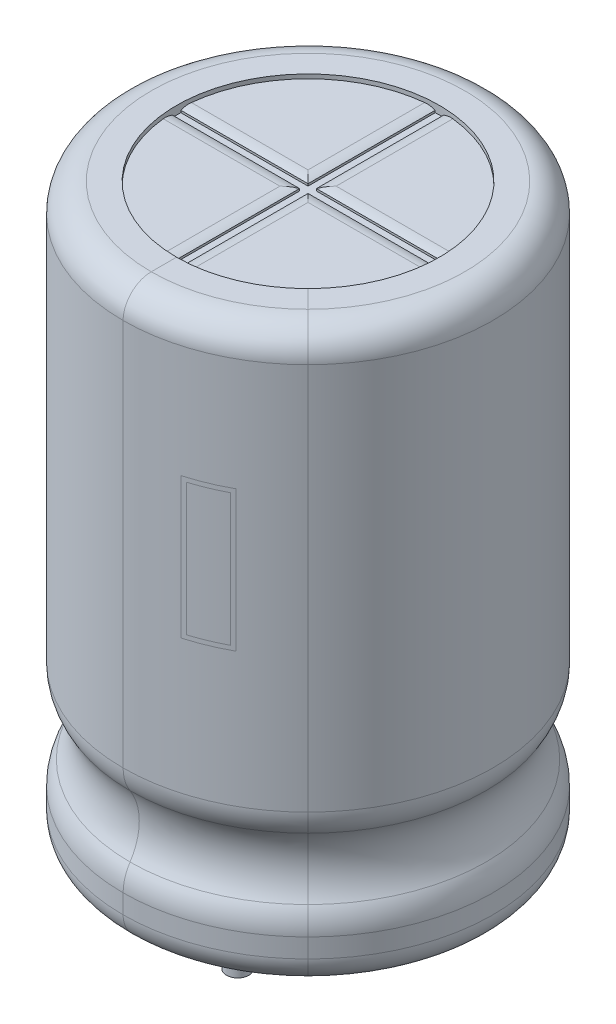
SolidWorks part; units mm, degrees
ref_plane "Front" through (0, 0, 0) normal (0, 0, 1) x (1, 0, 0)
ref_plane "Top" through (0, 0, 0) normal (0, 1, 0) x (1, 0, 0)
ref_plane "Right" through (0, 0, 0) normal (1, 0, 0) x (0, 0, -1)
sketch "Sketch1" plane through (0, 0, 0) normal (1, 0, 0) x (0, 0, -1)
  line L0 (0, 33.3732) -> (0, 0) construction
  line L1 (0, 0) -> (30.9962, 0) construction
  line L2 (0, 20) -> (4.675, 20)
  line L3 (4.675, 19) -> (4.675, 20.15)
  line L4 (5.575, 20.15) -> (4.675, 20.15)
  line L5 (6.575, 19.15) -> (6.575, 5.3721)
  line L6 (6.575, 1.5279) -> (6.575, 0.85)
  line L7 (5.425, -0.15) -> (5.575, -0.15)
  line L8 (5.425, 0) -> (5.425, -0.15)
  line L9 (5.425, 0) -> (0, 0)
  line L10 (0, 0) -> (0, 20)
  line L11 (0, 10) -> (2.9717, 10) construction
  line L12 (6, 3.45) -> (6, 1.4188) construction
  line L13 (0, 19) -> (4.675, 19)
  arc A0 (5.575, 20.15) -> (6.575, 19.15) centre (5.575, 19.15) cw
  arc A1 (6.575, 5.3721) -> (6.3286, 4.5483) centre (5.075, 5.3721) cw
  arc A2 (6.3286, 4.5483) -> (6.3286, 2.3517) centre (8, 3.45) ccw
  arc A3 (6.3286, 2.3517) -> (6.575, 1.5279) centre (5.075, 1.5279) cw
  arc A4 (6.575, 0.85) -> (5.575, -0.15) centre (5.575, 0.85) cw
  dimension "D6" = 1
  dimension "D7" = 1.5
  dimension "D9" = 12
  dimension "D10" = 2
  dimension "D1" = 20.3
  dimension "D2" = 13.15
  dimension "D3" = 0.15
  dimension "D4" = 9.35
  dimension "D5" = 1.15
  dimension "D8" = 3.45
  dimension "D11" = 1
revolve "Revolve1" add sketch "Sketch1" angle 360 about L0 region at (0, 19.5, -2.3375)
sketch "Sketch2" plane through (0, 0, 0) normal (1, 0, 0) x (0, 0, -1)
  line L0 (0, 32.8461) -> (0, 20) construction
  line L1 (0, 20) -> (4.675, 20) construction
  line L4 (-0.5, 20) -> (0.5, 20)
  line L5 (0.15, 19.925) -> (0.15, 19.85)
  line L6 (-0.15, 19.85) -> (-0.15, 19.925)
  line L7 (-0.15, 19.85) -> (0.15, 19.85)
  arc A0 (0.5, 20) -> (0.15, 19.925) centre (0.5, 19.1458) ccw
  arc A2 (-0.15, 19.925) -> (-0.5, 20) centre (-0.5, 19.1458) ccw
  dimension "D2" = 0.15
  dimension "D1" = 1
  dimension "D3" = 0.3
  dimension "D4" = 0.075
extrude "Cut-Extrude1" cut sketch "Sketch2" against normal through all both and the other way through all
pattern_circular "CirPattern1" count 2 over 90 about axis through (0, 33.3732, 0) along (0, 1, 0) of "Cut-Extrude1"
revolve "Revolve2" add sketch "Sketch1<3>" angle 360 about L0 region at (0, 9.7162, -3.2931)
sketch "Sketch1<3>" plane through (0, 0, 0) normal (1, 0, 0) x (0, 0, -1) same geometry as "Sketch1"
sketch "Sketch3" plane through (0, 20.15, 0) normal (0, 1, 0) x (1, 0, 0)
  line L0 (0, 0) -> (0, -8.8784)
  line L1 (0, 0) -> (6.9259, -6.9259)
  dimension "D1" = 45
split line "Split Line1"
ref_plane "Plane1" through (2.3246, 0, 5.6121) normal (-0.3827, 0, -0.9239) x (-0.9239, 0, 0.3827)
sketch "Sketch4" plane through (2.3246, 0, 5.6121) normal (-0.3827, 0, -0.9239) x (-0.9239, 0, 0.3827)
  line L0 (0, 0) -> (0, 20.7109) construction
  line L1 (0.75, 15.15) -> (-0.75, 15.15)
  line L2 (0.75, 15.15) -> (0.75, 10.15)
  line L3 (0.75, 10.15) -> (-0.75, 10.15)
  line L4 (-0.75, 15.15) -> (-0.75, 10.15)
  line L5 (2.1335, 20.15) -> (-2.1335, 20.15) construction
  line L6 (0.6, 15) -> (-0.6, 15)
  line L7 (-0.6, 15) -> (-0.6, 10.3)
  line L8 (0.6, 10.3) -> (-0.6, 10.3)
  line L9 (0.6, 15) -> (0.6, 10.3)
  dimension "D1" = 1.5
  dimension "D2" = 5
  dimension "D3" = 5
  dimension "D4" = 0.15
split line "Split Line2"
sketch "Sketch5" plane through (0, 0, 0) normal (0, -1, 0) x (1, 0, 0)
  line L0 (0, 2.5) -> (0, 0) construction
  line L1 (0, 0) -> (2.5084, 0) construction
  circle A0 centre (0, 2.5) radius 0.4
  circle A1 centre (0, -2.5) radius 0.4
  dimension "D1" = 0.8
  dimension "D2" = 5
extrude "Boss-Extrude1" add sketch "Sketch5" along normal blind 2.85
